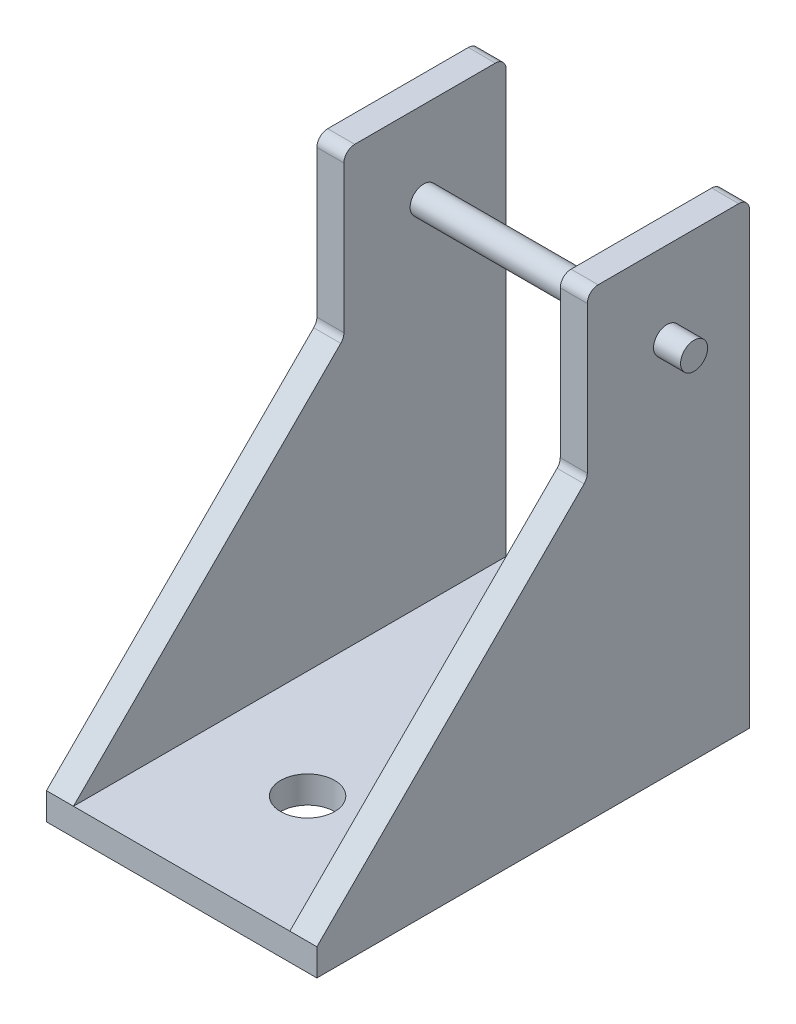
SolidWorks part; units mm, degrees
material "Plain Carbon Steel"
ref_plane "Front Plane" through (0, 0, 0) normal (0, 0, 1) x (1, 0, 0)
ref_plane "Top Plane" through (0, 0, 0) normal (0, 1, 0) x (1, 0, 0)
ref_plane "Right Plane" through (0, 0, 0) normal (1, 0, 0) x (0, 0, -1)
sketch "Sketch2" plane through (0, 0, 0) normal (0, 0, 1) x (1, 0, 0)
  line L1 (0, 0) -> (63.5, 0)
  line L2 (0, 0) -> (0, 6.35)
  line L3 (0, 6.35) -> (63.5, 6.35)
  line L4 (63.5, 0) -> (63.5, 6.35)
  dimension "D1" = 6.35
  dimension "D2" = 63.5
extrude "Base" add sketch "Sketch2" along normal blind 101.6
ref_plane "Plane1" through (31.75, 0, 0) normal (-1, 0, 0) x (0, 0, 1)
sketch "Sketch4" plane through (63.5, 0, 0) normal (1, 0, 0) x (0, 0, -1)
  line L0 (0, 107.95) -> (0, 6.35)
  line L1 (0, 107.95) -> (-38.1, 107.95)
  line L2 (0, 6.35) -> (-101.6, 6.35)
  line L3 (-101.6, 6.35) -> (0, 6.35) construction
  line L4 (-101.6, 6.35) -> (-38.1, 69.85)
  line L5 (-101.6, 0) -> (-101.6, 6.35) construction
  line L6 (-38.1, 107.95) -> (-38.1, 69.85)
  dimension "D1" = 38.1
  dimension "D2" = 45
extrude "Rib" add sketch "Sketch4" against normal blind 6.35
mirror "RibCopy" about plane through (31.75, 0, 0) normal (-1, 0, 0) of "Rib"
sketch "Sketch5" plane through (57.15, 0, 0) normal (-1, 0, 0) x (0, 0, 1)
  circle A0 centre (19.3743, 88.6032) radius 3.175
  dimension "D1" = 6.35
fillet "Fillet2" radius 2.54 6 edges at (60.325, 107.95, 0) (60.325, 69.85, 38.1) (60.325, 107.95, 38.1) (3.175, 107.95, 0) (3.175, 107.95, 38.1) (3.175, 69.85, 38.1)
extrude "Cut-Extrude1" cut sketch "Sketch5" against normal through all and the other way through all
extrude "Boss-Extrude1" add sketch "Sketch5<2>" along normal blind 63.5 and the other way blind 12.7 separate body
sketch "Sketch5<2>" plane through (57.15, 0, 0) normal (-1, 0, 0) x (0, 0, 1) same geometry as "Sketch5"
sketch "Sketch6" plane through (0, 6.35, 0) normal (0, 1, 0) x (-1, 0, 0)
  line L0 (-57.15, 101.6) -> (-57.15, 0) construction
  line L1 (-31.75, 72.0236) -> (-31.75, 32.1145) construction
  circle A0 centre (-31.75, 72.0236) radius 6.35
  circle A1 centre (-31.75, 32.1145) radius 6.35
  dimension "D1" = 12.7
  dimension "D2" = 25.4
extrude "Cut-Extrude2" cut sketch "Sketch6" against normal up to next (6.35 mm away)
